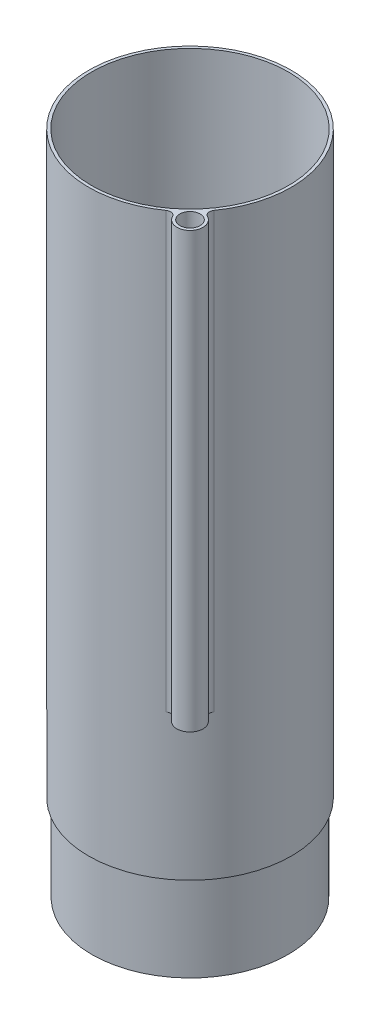
SolidWorks part; units mm, degrees
ref_plane "Front Plane" through (0, 0, 0) normal (0, 0, 1) x (1, 0, 0)
ref_plane "Top Plane" through (0, 0, 0) normal (0, 1, 0) x (1, 0, 0)
ref_plane "Right Plane" through (0, 0, 0) normal (1, 0, 0) x (0, 0, -1)
sketch "Sketch1" plane through (0, 0, 0) normal (0, 1, 0) x (1, 0, 0)
  circle A0 centre (0, 0) radius 35
  circle A1 centre (0, 0) radius 34
  dimension "D1" = 70
  dimension "D2" = 1
extrude "Boss-Extrude1" add sketch "Sketch1" along normal blind 200
sketch "Sketch2" plane through (0, 0, 0) normal (0, -1, 0) x (1, 0, 0)
  circle A0 centre (0, 0) radius 34 construction
  circle A1 centre (0, 0) radius 34
  circle A2 centre (0, 0) radius 32.9
  dimension "D1" = 1.1
extrude "Boss-Extrude2" add sketch "Sketch2" against normal blind 2
sketch "Sketch3" plane through (0, 0, 0) normal (0, -1, 0) x (1, 0, 0)
  circle A0 centre (0, 0) radius 32.9 construction
  circle A1 centre (0, 0) radius 32.9
  circle A2 centre (0, 0) radius 33.9
  dimension "D1" = 1
extrude "Boss-Extrude3" add sketch "Sketch3" along normal blind 30
sketch "Sketch4" plane through (0, -30, 0) normal (0, -1, 0) x (1, 0, 0)
  circle A0 centre (0, 0) radius 33.9 construction
  circle A1 centre (0, 0) radius 33.9
extrude "Boss-Extrude4" add sketch "Sketch4" against normal blind 2
sketch "Sketch5" plane through (0, -30, 0) normal (0, -1, 0) x (1, 0, 0)
  circle A0 centre (0, 0) radius 5
  dimension "D1" = 10
extrude "Cut-Extrude1" cut sketch "Sketch5" against normal blind 2
sketch "Sketch7" plane through (0, 2, 0) normal (0, 1, 0) x (1, 0, 0)
  line L0 (0, 0) -> (34, 0) construction
  circle A0 centre (0, 0) radius 34 construction
  circle A1 centre (32, 0) radius 3
  circle A2 centre (0, 0) radius 35 construction
  circle A3 centre (32, 0) radius 2
  point P8 (35, 0)
  dimension "D1" = 6
  dimension "D2" = 1
extrude "Boss-Extrude8" add sketch "Sketch7" along normal blind 160
fillet "Fillet2" radius 2 2 edges at (33.9219, 82, 2.3036) (33.9219, 82, -2.3036)
sketch "Sketch8" plane through (0, -28, 0) normal (0, 1, 0) x (1, 0, 0)
  line L0 (35, 0) -> (0, 0) construction
  circle A0 centre (0, 0) radius 35 construction
  circle A1 centre (31.189, 0) radius 2
  dimension "D1" = 4
extrude "Cut-Extrude2" cut sketch "Sketch8" against normal blind 2
sketch "Sketch9" plane through (0, 200, 0) normal (0, 1, 0) x (1, 0, 0)
  line L0 (0, 0) -> (31.9809, -31.9809) construction
  circle A0 centre (27.2236, -27.2236) radius 3.5
  circle A1 centre (0, 0) radius 35 construction
  circle A2 centre (27.2236, -27.2236) radius 4.5
  point P5 (24.7487, -24.7487)
  dimension "D1" = 7
  dimension "D2" = 1
extrude "Boss-Extrude9" add sketch "Sketch9" against normal blind 150
fillet "Fillet3" radius 2 2 edges at (26.5808, 125, 22.7698) (22.7698, 125, 26.5808)
